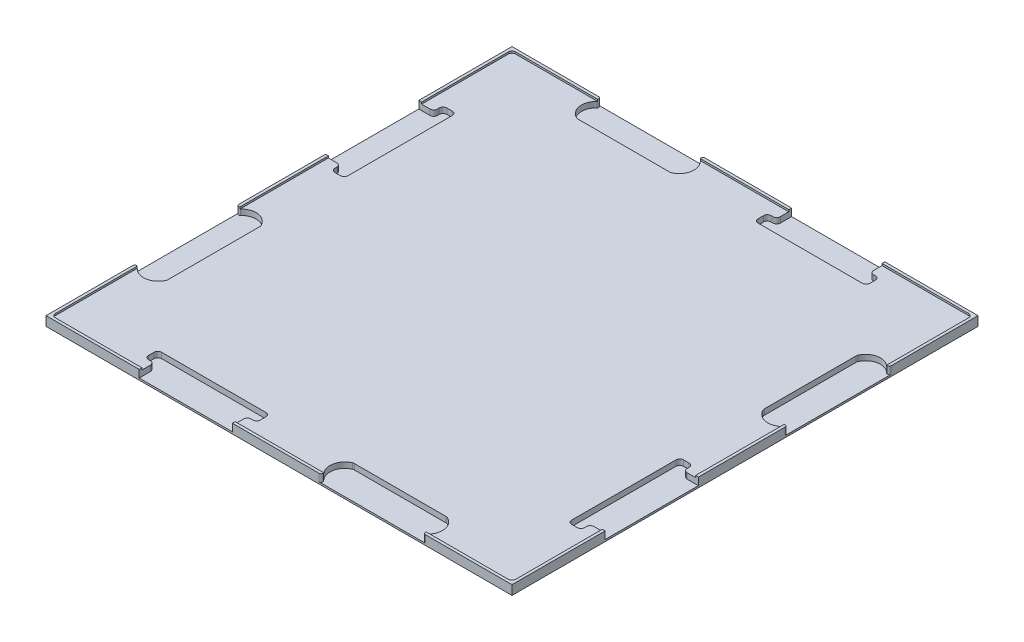
SolidWorks part; units mm, degrees
material "99.5% Aluminum Oxide"
ref_plane "Front Plane" through (0, 0, 0) normal (0, 0, 1) x (1, 0, 0)
ref_plane "Top Plane" through (0, 0, 0) normal (0, 1, 0) x (1, 0, 0)
ref_plane "Right Plane" through (0, 0, 0) normal (1, 0, 0) x (0, 0, -1)
sketch "Sketch1" plane through (0, 0, 0) normal (0, 1, 0) x (1, 0, 0)
  line L1 (-125, -125) -> (125, -125)
  line L2 (-125, -125) -> (-125, 125)
  line L3 (-125, 125) -> (125, 125)
  line L4 (125, -125) -> (125, 125)
  line L5 (-125, -125) -> (125, 125) construction
  line L6 (-125, 125) -> (125, -125) construction
  point P0 (0, 0)
  dimension "D1" = 250
extrude "Boss-Extrude1" add sketch "Sketch1" along normal mid plane 5
sketch "Sketch2" plane through (0, 2.5, 0) normal (0, 1, 0) x (1, 0, 0)
  line L0 (125, 125) -> (-125, 125) construction
  line L1 (-123.5, -123.5) -> (123.5, -123.5)
  line L2 (-123.5, -123.5) -> (-123.5, 123.5)
  line L3 (-123.5, 123.5) -> (123.5, 123.5)
  line L4 (123.5, -123.5) -> (123.5, 123.5)
  line L5 (-123.5, -123.5) -> (123.5, 123.5) construction
  line L6 (-123.5, 123.5) -> (123.5, -123.5) construction
  point P0 (0, 0)
  dimension "D1" = 1.5
extrude "Cut-Extrude1" cut sketch "Sketch2" against normal blind 1
sketch "Sketch3" plane through (0, 1.5, 0) normal (0, 1, 0) x (1, 0, 0)
  line L7 (-79.5, 103) -> (-79.5, 85)
  line L8 (-79.5, 103) -> (-61.5, 103)
  line L486 (-125, 125) -> (-125, -125) construction
  line L487 (-103, 103) -> (-85, 103)
  line L488 (-103, 103) -> (-103, 85)
  line L489 (-103, 85) -> (-85, 85)
  line L490 (-85, 103) -> (-85, 85)
  line L491 (125, 125) -> (-125, 125) construction
  line L492 (-61.5, 103) -> (-61.5, 85)
  line L493 (-79.5, 85) -> (-61.5, 85)
  line L494 (-56, 103) -> (-56, 85)
  line L495 (-56, 103) -> (-38, 103)
  line L496 (-38, 103) -> (-38, 85)
  line L497 (-56, 85) -> (-38, 85)
  line L498 (-32.5, 103) -> (-32.5, 85)
  line L499 (-32.5, 103) -> (-14.5, 103)
  line L500 (-14.5, 103) -> (-14.5, 85)
  line L501 (-32.5, 85) -> (-14.5, 85)
  line L502 (-9, 103) -> (-9, 85)
  line L503 (-9, 103) -> (9, 103)
  line L504 (9, 103) -> (9, 85)
  line L505 (-9, 85) -> (9, 85)
  line L506 (14.5, 103) -> (14.5, 85)
  line L507 (14.5, 103) -> (32.5, 103)
  line L508 (32.5, 103) -> (32.5, 85)
  line L509 (14.5, 85) -> (32.5, 85)
  line L510 (38, 103) -> (38, 85)
  line L511 (38, 103) -> (56, 103)
  line L512 (56, 103) -> (56, 85)
  line L513 (38, 85) -> (56, 85)
  line L514 (61.5, 103) -> (61.5, 85)
  line L515 (61.5, 103) -> (79.5, 103)
  line L516 (79.5, 103) -> (79.5, 85)
  line L517 (61.5, 85) -> (79.5, 85)
  line L518 (85, 103) -> (85, 85)
  line L519 (85, 103) -> (103, 103)
  line L520 (103, 103) -> (103, 85)
  line L521 (85, 85) -> (103, 85)
  line L522 (-79.5, 79.5) -> (-79.5, 61.5)
  line L523 (-79.5, 79.5) -> (-61.5, 79.5)
  line L524 (-61.5, 79.5) -> (-61.5, 61.5)
  line L525 (-79.5, 61.5) -> (-61.5, 61.5)
  line L526 (-56, 79.5) -> (-56, 61.5)
  line L527 (-56, 79.5) -> (-38, 79.5)
  line L528 (-38, 79.5) -> (-38, 61.5)
  line L529 (-56, 61.5) -> (-38, 61.5)
  line L530 (-32.5, 79.5) -> (-32.5, 61.5)
  line L531 (-32.5, 79.5) -> (-14.5, 79.5)
  line L532 (-14.5, 79.5) -> (-14.5, 61.5)
  line L533 (-32.5, 61.5) -> (-14.5, 61.5)
  line L534 (-9, 79.5) -> (-9, 61.5)
  line L535 (-9, 79.5) -> (9, 79.5)
  line L536 (9, 79.5) -> (9, 61.5)
  line L537 (-9, 61.5) -> (9, 61.5)
  line L538 (14.5, 79.5) -> (14.5, 61.5)
  line L539 (14.5, 79.5) -> (32.5, 79.5)
  line L540 (32.5, 79.5) -> (32.5, 61.5)
  line L541 (14.5, 61.5) -> (32.5, 61.5)
  line L542 (38, 79.5) -> (38, 61.5)
  line L543 (38, 79.5) -> (56, 79.5)
  line L544 (56, 79.5) -> (56, 61.5)
  line L545 (38, 61.5) -> (56, 61.5)
  line L546 (61.5, 79.5) -> (61.5, 61.5)
  line L547 (61.5, 79.5) -> (79.5, 79.5)
  line L548 (79.5, 79.5) -> (79.5, 61.5)
  line L549 (61.5, 61.5) -> (79.5, 61.5)
  line L550 (85, 79.5) -> (85, 61.5)
  line L551 (85, 79.5) -> (103, 79.5)
  line L552 (103, 79.5) -> (103, 61.5)
  line L553 (85, 61.5) -> (103, 61.5)
  line L554 (-79.5, 56) -> (-79.5, 38)
  line L555 (-79.5, 56) -> (-61.5, 56)
  line L556 (-61.5, 56) -> (-61.5, 38)
  line L557 (-79.5, 38) -> (-61.5, 38)
  line L558 (-56, 56) -> (-56, 38)
  line L559 (-56, 56) -> (-38, 56)
  line L560 (-38, 56) -> (-38, 38)
  line L561 (-56, 38) -> (-38, 38)
  line L562 (-32.5, 56) -> (-32.5, 38)
  line L563 (-32.5, 56) -> (-14.5, 56)
  line L564 (-14.5, 56) -> (-14.5, 38)
  line L565 (-32.5, 38) -> (-14.5, 38)
  line L566 (-9, 56) -> (-9, 38)
  line L567 (-9, 56) -> (9, 56)
  line L568 (9, 56) -> (9, 38)
  line L569 (-9, 38) -> (9, 38)
  line L570 (14.5, 56) -> (14.5, 38)
  line L571 (14.5, 56) -> (32.5, 56)
  line L572 (32.5, 56) -> (32.5, 38)
  line L573 (14.5, 38) -> (32.5, 38)
  line L574 (38, 56) -> (38, 38)
  line L575 (38, 56) -> (56, 56)
  line L576 (56, 56) -> (56, 38)
  line L577 (38, 38) -> (56, 38)
  line L578 (61.5, 56) -> (61.5, 38)
  line L579 (61.5, 56) -> (79.5, 56)
  line L580 (79.5, 56) -> (79.5, 38)
  line L581 (61.5, 38) -> (79.5, 38)
  line L582 (85, 56) -> (85, 38)
  line L583 (85, 56) -> (103, 56)
  line L584 (103, 56) -> (103, 38)
  line L585 (85, 38) -> (103, 38)
  line L586 (-79.5, 32.5) -> (-79.5, 14.5)
  line L587 (-79.5, 32.5) -> (-61.5, 32.5)
  line L588 (-61.5, 32.5) -> (-61.5, 14.5)
  line L589 (-79.5, 14.5) -> (-61.5, 14.5)
  line L590 (-56, 32.5) -> (-56, 14.5)
  line L591 (-56, 32.5) -> (-38, 32.5)
  line L592 (-38, 32.5) -> (-38, 14.5)
  line L593 (-56, 14.5) -> (-38, 14.5)
  line L594 (-32.5, 32.5) -> (-32.5, 14.5)
  line L595 (-32.5, 32.5) -> (-14.5, 32.5)
  line L596 (-14.5, 32.5) -> (-14.5, 14.5)
  line L597 (-32.5, 14.5) -> (-14.5, 14.5)
  line L598 (-9, 32.5) -> (-9, 14.5)
  line L599 (-9, 32.5) -> (9, 32.5)
  line L600 (9, 32.5) -> (9, 14.5)
  line L601 (-9, 14.5) -> (9, 14.5)
  line L602 (14.5, 32.5) -> (14.5, 14.5)
  line L603 (14.5, 32.5) -> (32.5, 32.5)
  line L604 (32.5, 32.5) -> (32.5, 14.5)
  line L605 (14.5, 14.5) -> (32.5, 14.5)
  line L606 (38, 32.5) -> (38, 14.5)
  line L607 (38, 32.5) -> (56, 32.5)
  line L608 (56, 32.5) -> (56, 14.5)
  line L609 (38, 14.5) -> (56, 14.5)
  line L610 (61.5, 32.5) -> (61.5, 14.5)
  line L611 (61.5, 32.5) -> (79.5, 32.5)
  line L612 (79.5, 32.5) -> (79.5, 14.5)
  line L613 (61.5, 14.5) -> (79.5, 14.5)
  line L614 (85, 32.5) -> (85, 14.5)
  line L615 (85, 32.5) -> (103, 32.5)
  line L616 (103, 32.5) -> (103, 14.5)
  line L617 (85, 14.5) -> (103, 14.5)
  line L618 (-79.5, 9) -> (-79.5, -9)
  line L619 (-79.5, 9) -> (-61.5, 9)
  line L620 (-61.5, 9) -> (-61.5, -9)
  line L621 (-79.5, -9) -> (-61.5, -9)
  line L622 (-56, 9) -> (-56, -9)
  line L623 (-56, 9) -> (-38, 9)
  line L624 (-38, 9) -> (-38, -9)
  line L625 (-56, -9) -> (-38, -9)
  line L626 (-32.5, 9) -> (-32.5, -9)
  line L627 (-32.5, 9) -> (-14.5, 9)
  line L628 (-14.5, 9) -> (-14.5, -9)
  line L629 (-32.5, -9) -> (-14.5, -9)
  line L630 (-9, 9) -> (-9, -9)
  line L631 (-9, 9) -> (9, 9)
  line L632 (9, 9) -> (9, -9)
  line L633 (-9, -9) -> (9, -9)
  line L634 (14.5, 9) -> (14.5, -9)
  line L635 (14.5, 9) -> (32.5, 9)
  line L636 (32.5, 9) -> (32.5, -9)
  line L637 (14.5, -9) -> (32.5, -9)
  line L638 (38, 9) -> (38, -9)
  line L639 (38, 9) -> (56, 9)
  line L640 (56, 9) -> (56, -9)
  line L641 (38, -9) -> (56, -9)
  line L642 (61.5, 9) -> (61.5, -9)
  line L643 (61.5, 9) -> (79.5, 9)
  line L644 (79.5, 9) -> (79.5, -9)
  line L645 (61.5, -9) -> (79.5, -9)
  line L646 (85, 9) -> (85, -9)
  line L647 (85, 9) -> (103, 9)
  line L648 (103, 9) -> (103, -9)
  line L649 (85, -9) -> (103, -9)
  line L650 (-79.5, -14.5) -> (-79.5, -32.5)
  line L651 (-79.5, -14.5) -> (-61.5, -14.5)
  line L652 (-61.5, -14.5) -> (-61.5, -32.5)
  line L653 (-79.5, -32.5) -> (-61.5, -32.5)
  line L654 (-56, -14.5) -> (-56, -32.5)
  line L655 (-56, -14.5) -> (-38, -14.5)
  line L656 (-38, -14.5) -> (-38, -32.5)
  line L657 (-56, -32.5) -> (-38, -32.5)
  line L658 (-32.5, -14.5) -> (-32.5, -32.5)
  line L659 (-32.5, -14.5) -> (-14.5, -14.5)
  line L660 (-14.5, -14.5) -> (-14.5, -32.5)
  line L661 (-32.5, -32.5) -> (-14.5, -32.5)
  line L662 (-9, -14.5) -> (-9, -32.5)
  line L663 (-9, -14.5) -> (9, -14.5)
  line L664 (9, -14.5) -> (9, -32.5)
  line L665 (-9, -32.5) -> (9, -32.5)
  line L666 (14.5, -14.5) -> (14.5, -32.5)
  line L667 (14.5, -14.5) -> (32.5, -14.5)
  line L668 (32.5, -14.5) -> (32.5, -32.5)
  line L669 (14.5, -32.5) -> (32.5, -32.5)
  line L670 (38, -14.5) -> (38, -32.5)
  line L671 (38, -14.5) -> (56, -14.5)
  line L672 (56, -14.5) -> (56, -32.5)
  line L673 (38, -32.5) -> (56, -32.5)
  line L674 (61.5, -14.5) -> (61.5, -32.5)
  line L675 (61.5, -14.5) -> (79.5, -14.5)
  line L676 (79.5, -14.5) -> (79.5, -32.5)
  line L677 (61.5, -32.5) -> (79.5, -32.5)
  line L678 (85, -14.5) -> (85, -32.5)
  line L679 (85, -14.5) -> (103, -14.5)
  line L680 (103, -14.5) -> (103, -32.5)
  line L681 (85, -32.5) -> (103, -32.5)
  line L682 (-79.5, -38) -> (-79.5, -56)
  line L683 (-79.5, -38) -> (-61.5, -38)
  line L684 (-61.5, -38) -> (-61.5, -56)
  line L685 (-79.5, -56) -> (-61.5, -56)
  line L686 (-56, -38) -> (-56, -56)
  line L687 (-56, -38) -> (-38, -38)
  line L688 (-38, -38) -> (-38, -56)
  line L689 (-56, -56) -> (-38, -56)
  line L690 (-32.5, -38) -> (-32.5, -56)
  line L691 (-32.5, -38) -> (-14.5, -38)
  line L692 (-14.5, -38) -> (-14.5, -56)
  line L693 (-32.5, -56) -> (-14.5, -56)
  line L694 (-9, -38) -> (-9, -56)
  line L695 (-9, -38) -> (9, -38)
  line L696 (9, -38) -> (9, -56)
  line L697 (-9, -56) -> (9, -56)
  line L698 (14.5, -38) -> (14.5, -56)
  line L699 (14.5, -38) -> (32.5, -38)
  line L700 (32.5, -38) -> (32.5, -56)
  line L701 (14.5, -56) -> (32.5, -56)
  line L702 (38, -38) -> (38, -56)
  line L703 (38, -38) -> (56, -38)
  line L704 (56, -38) -> (56, -56)
  line L705 (38, -56) -> (56, -56)
  line L706 (61.5, -38) -> (61.5, -56)
  line L707 (61.5, -38) -> (79.5, -38)
  line L708 (79.5, -38) -> (79.5, -56)
  line L709 (61.5, -56) -> (79.5, -56)
  line L710 (85, -38) -> (85, -56)
  line L711 (85, -38) -> (103, -38)
  line L712 (103, -38) -> (103, -56)
  line L713 (85, -56) -> (103, -56)
  line L714 (-79.5, -61.5) -> (-79.5, -79.5)
  line L715 (-79.5, -61.5) -> (-61.5, -61.5)
  line L716 (-61.5, -61.5) -> (-61.5, -79.5)
  line L717 (-79.5, -79.5) -> (-61.5, -79.5)
  line L718 (-56, -61.5) -> (-56, -79.5)
  line L719 (-56, -61.5) -> (-38, -61.5)
  line L720 (-38, -61.5) -> (-38, -79.5)
  line L721 (-56, -79.5) -> (-38, -79.5)
  line L722 (-32.5, -61.5) -> (-32.5, -79.5)
  line L723 (-32.5, -61.5) -> (-14.5, -61.5)
  line L724 (-14.5, -61.5) -> (-14.5, -79.5)
  line L725 (-32.5, -79.5) -> (-14.5, -79.5)
  line L726 (-9, -61.5) -> (-9, -79.5)
  line L727 (-9, -61.5) -> (9, -61.5)
  line L728 (9, -61.5) -> (9, -79.5)
  line L729 (-9, -79.5) -> (9, -79.5)
  line L730 (14.5, -61.5) -> (14.5, -79.5)
  line L731 (14.5, -61.5) -> (32.5, -61.5)
  line L732 (32.5, -61.5) -> (32.5, -79.5)
  line L733 (14.5, -79.5) -> (32.5, -79.5)
  line L734 (38, -61.5) -> (38, -79.5)
  line L735 (38, -61.5) -> (56, -61.5)
  line L736 (56, -61.5) -> (56, -79.5)
  line L737 (38, -79.5) -> (56, -79.5)
  line L738 (61.5, -61.5) -> (61.5, -79.5)
  line L739 (61.5, -61.5) -> (79.5, -61.5)
  line L740 (79.5, -61.5) -> (79.5, -79.5)
  line L741 (61.5, -79.5) -> (79.5, -79.5)
  line L742 (85, -61.5) -> (85, -79.5)
  line L743 (85, -61.5) -> (103, -61.5)
  line L744 (103, -61.5) -> (103, -79.5)
  line L745 (85, -79.5) -> (103, -79.5)
  line L746 (-79.5, -85) -> (-79.5, -103)
  line L747 (-79.5, -85) -> (-61.5, -85)
  line L748 (-61.5, -85) -> (-61.5, -103)
  line L749 (-79.5, -103) -> (-61.5, -103)
  line L750 (-56, -85) -> (-56, -103)
  line L751 (-56, -85) -> (-38, -85)
  line L752 (-38, -85) -> (-38, -103)
  line L753 (-56, -103) -> (-38, -103)
  line L754 (-32.5, -85) -> (-32.5, -103)
  line L755 (-32.5, -85) -> (-14.5, -85)
  line L756 (-14.5, -85) -> (-14.5, -103)
  line L757 (-32.5, -103) -> (-14.5, -103)
  line L758 (-9, -85) -> (-9, -103)
  line L759 (-9, -85) -> (9, -85)
  line L760 (9, -85) -> (9, -103)
  line L761 (-9, -103) -> (9, -103)
  line L762 (14.5, -85) -> (14.5, -103)
  line L763 (14.5, -85) -> (32.5, -85)
  line L764 (32.5, -85) -> (32.5, -103)
  line L765 (14.5, -103) -> (32.5, -103)
  line L766 (38, -85) -> (38, -103)
  line L767 (38, -85) -> (56, -85)
  line L768 (56, -85) -> (56, -103)
  line L769 (38, -103) -> (56, -103)
  line L770 (61.5, -85) -> (61.5, -103)
  line L771 (61.5, -85) -> (79.5, -85)
  line L772 (79.5, -85) -> (79.5, -103)
  line L773 (61.5, -103) -> (79.5, -103)
  line L774 (85, -85) -> (85, -103)
  line L775 (85, -85) -> (103, -85)
  line L776 (103, -85) -> (103, -103)
  line L777 (85, -103) -> (103, -103)
  line L778 (-103, 79.5) -> (-103, 61.5)
  line L779 (-103, 79.5) -> (-85, 79.5)
  line L780 (-85, 79.5) -> (-85, 61.5)
  line L781 (-103, 61.5) -> (-85, 61.5)
  line L782 (-103, 56) -> (-103, 38)
  line L783 (-103, 56) -> (-85, 56)
  line L784 (-85, 56) -> (-85, 38)
  line L785 (-103, 38) -> (-85, 38)
  line L786 (-103, 32.5) -> (-103, 14.5)
  line L787 (-103, 32.5) -> (-85, 32.5)
  line L788 (-85, 32.5) -> (-85, 14.5)
  line L789 (-103, 14.5) -> (-85, 14.5)
  line L790 (-103, 9) -> (-103, -9)
  line L791 (-103, 9) -> (-85, 9)
  line L792 (-85, 9) -> (-85, -9)
  line L793 (-103, -9) -> (-85, -9)
  line L794 (-103, -14.5) -> (-103, -32.5)
  line L795 (-103, -14.5) -> (-85, -14.5)
  line L796 (-85, -14.5) -> (-85, -32.5)
  line L797 (-103, -32.5) -> (-85, -32.5)
  line L798 (-103, -38) -> (-103, -56)
  line L799 (-103, -38) -> (-85, -38)
  line L800 (-85, -38) -> (-85, -56)
  line L801 (-103, -56) -> (-85, -56)
  line L802 (-103, -61.5) -> (-103, -79.5)
  line L803 (-103, -61.5) -> (-85, -61.5)
  line L804 (-85, -61.5) -> (-85, -79.5)
  line L805 (-103, -79.5) -> (-85, -79.5)
  line L806 (-103, -85) -> (-103, -103)
  line L807 (-103, -85) -> (-85, -85)
  line L808 (-85, -85) -> (-85, -103)
  line L809 (-103, -103) -> (-85, -103)
  line L810 (-103, 103) -> (-79.5, 103) construction
  line L811 (-103, 103) -> (-103, 79.5) construction
  line L817 (125, -125) -> (125, 125) construction
  dimension "D1" = 18
  dimension "D2" = 22
  dimension "D3" = 22
  dimension "D4" = 90
  dimension "D6" = 23.5
  dimension "D7" = 9
  dimension "D5" = 23.5
  dimension "D9" = 22
  dimension "D10" = 5.5
  dimension "D8" = 9
extrude "Cut-Extrude3" [suppressed] cut sketch "Sketch3" against normal blind 1
sketch "Sketch5" plane through (0, 2.5, 0) normal (0, 1, 0) x (1, 0, 0)
  line L0 (-75, -125) -> (-75, -117)
  line L1 (-50, -125) -> (-50, 49875) construction
  line L2 (-125, -125) -> (125, -125) construction
  line L3 (-75, -117) -> (-80, -117)
  line L4 (-80, -117) -> (-80, -110)
  line L5 (-80, -110) -> (-20, -110)
  line L6 (-20, -110) -> (-20, -117)
  line L7 (-20, -117) -> (-25, -117)
  line L8 (-25, -117) -> (-25, -125)
  line L9 (-25, -125) -> (-75, -125)
  line L10 (-125, 125) -> (-125, -125) construction
  line L11 (125, -125) -> (125, 125) construction
  line L12 (25, -125) -> (75, -125)
  line L13 (25, -125) -> (25, -110) construction
  line L14 (25, -110) -> (75, -110)
  line L15 (75, -125) -> (75, -110) construction
  arc A0 (25, -110) -> (25, -125) centre (27.7839, -117.5) ccw
  arc A1 (75, -110) -> (75, -125) centre (72.2161, -117.5) cw
  point P13 (-50, -125)
  point P14 (-50, -110)
  dimension "D9" = 8
  dimension "D1" = 5
  dimension "D2" = 7
  dimension "D3" = 50
  dimension "D4" = 50
  dimension "D5" = 15
  dimension "D6" = 50
  dimension "D7" = 15
  dimension "D8" = 50
extrude "Cut-Extrude4" cut sketch "Sketch5" against normal blind 4
ref_axis "Axis1" through (0, -36.4707, 0) along (0, 1, 0)
pattern_circular "CirPattern1" count 4 over 360 about axis through (0, -36.4707, 0) along (0, 1, 0) of "Cut-Extrude4"
fillet "Fillet2" radius 2 36 edges at (-117, 0, -25) (-117, 0, -20) (-110, 0, -20) (-110, 0, -80) (-117, 0, -80) (-123.5, 2, -123.5) (-75, 0, -110) (-25, 0, -110) (25, 0, -117) (20, 0, -117) (20, 0, -110) (80, 0, -110) (80, 0, -117) (75, 0, -117) (123.5, 2, -123.5) (110, 0, -75) (110, 0, -25) (117, 0, 25) (117, 0, 20) (110, 0, 20) (110, 0, 80) (117, 0, 80) (117, 0, 75) (123.5, 2, 123.5) (75, 0, 110) (25, 0, 110) (-25, 0, 117) (-20, 0, 117) (-20, 0, 110) (-80, 0, 110) (-80, 0, 117) (-75, 0, 117) (-123.5, 2, 123.5) (-110, 0, 75) (-110, 0, 25) (-117, 0, -75)
fillet "Fillet3" radius 1 8 edges at (-75, 0.5, -125) (-25, 0.5, -125) (125, 0.5, -25) (125, 0.5, -75) (25, 0.5, 125) (75, 0.5, 125) (-125, 0.5, 75) (-125, 0.5, 25)
